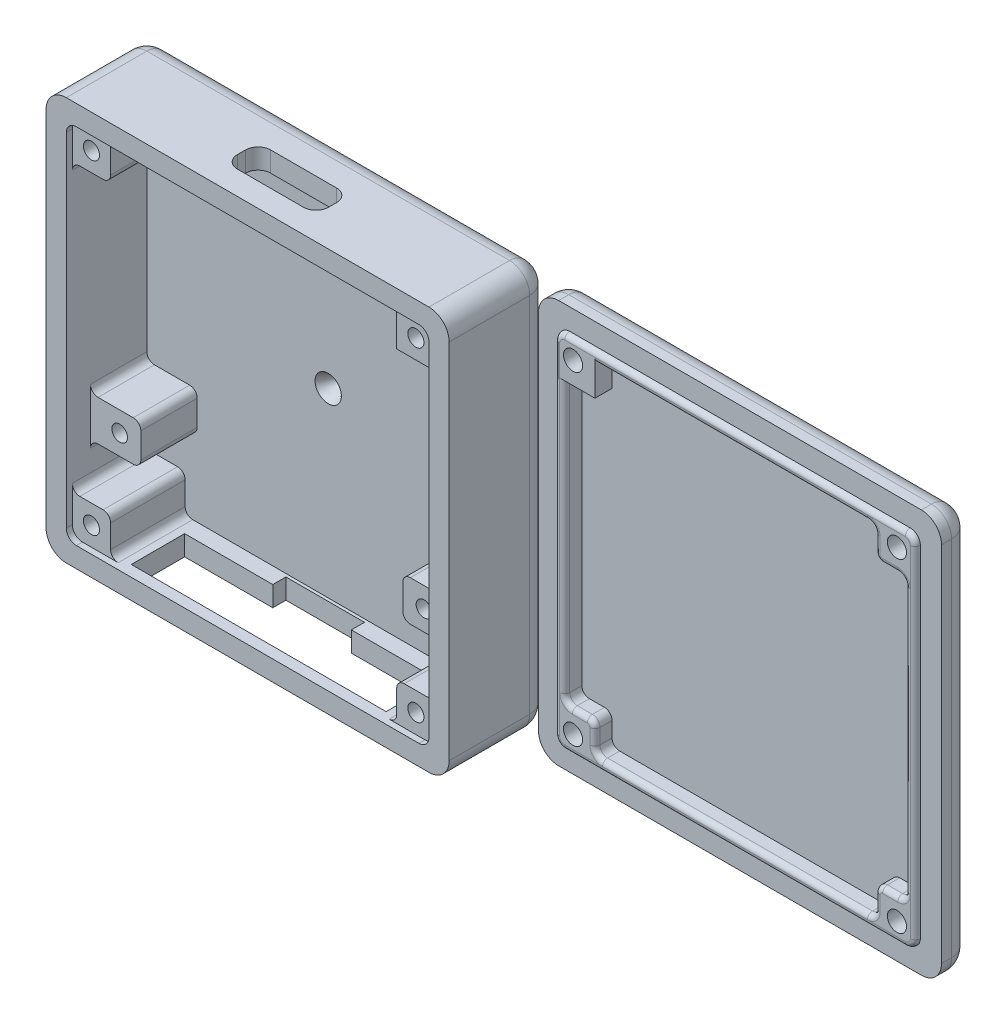
SolidWorks part; units mm, degrees
ref_plane "前视基准面" through (0, 0, 0) normal (0, 0, 1) x (1, 0, 0)
ref_plane "上视基准面" through (0, 0, 0) normal (0, 1, 0) x (1, 0, 0)
ref_plane "右视基准面" through (0, 0, 0) normal (1, 0, 0) x (0, 0, -1)
other "Configuration Table"
sketch "草图1" plane through (0, 0, 0) normal (0, 0, 1) x (1, 0, 0)
  line L6 (-20, 20) -> (20, 20)
  line L11 (-20, 20) -> (-20, -20)
  line L12 (-20, -20) -> (20, -20)
  line L13 (20, 20) -> (20, -20)
  line L14 (-20, 20) -> (20, -20) construction
  line L15 (-20, -20) -> (20, 20) construction
  point P0 (0, 0)
  dimension "D1" = 40
  dimension "D2" = 40
extrude "凸台-拉伸3" add sketch "草图1" along normal blind 10
fillet "圆角1" radius 2 8 edges at (20, -20, 5) (-20, -20, 5) (20, 20, 5) (-20, 20, 5) (0, 20, 0) (-20, 0, 0) (0, -20, 0) (20, 0, 0)
sketch "草图5" plane through (0, 0, 10) normal (0, 0, 1) x (1, 0, 0)
  line L1 (-17, 18) -> (17, 18)
  line L2 (-18, 17) -> (-18, -17)
  line L3 (-17, -18) -> (17, -18)
  line L4 (18, 17) -> (18, -17)
  line L5 (-18, 18) -> (18, -18) construction
  line L6 (-18, -18) -> (18, 18) construction
  arc A0 (-18, -17) -> (-17, -18) centre (-17, -17) ccw
  arc A1 (17, -18) -> (18, -17) centre (17, -17) ccw
  arc A2 (18, 17) -> (17, 18) centre (17, 17) ccw
  arc A3 (-17, 18) -> (-18, 17) centre (-17, 17) ccw
  point P0 (0, 0)
  dimension "D3" = 1
  dimension "D4" = 1
  dimension "D1" = 36
  dimension "D2" = 36
extrude "切除-拉伸2" cut sketch "草图5" against normal blind 8
sketch "草图6" plane through (0, 0, 0) normal (0, 0, -1) x (-1, 0, 0)
  line L0 (-18, -14.2) -> (-14.2, -14.2)
  line L1 (-18, -17) -> (-18, 17) construction
  line L2 (-14.2, -14.2) -> (-14.2, -18)
  line L3 (17, -18) -> (-17, -18) construction
  line L4 (14.2, 18) -> (14.2, 14.2)
  line L5 (-17, 18) -> (17, 18) construction
  line L6 (14.2, 14.2) -> (18, 14.2)
  line L7 (18, 17) -> (18, -17) construction
  line L8 (-18, -14.2) -> (-14.2, -18) construction
  line L9 (-14.2, -14.2) -> (-17.7071, -17.7071) construction
  line L10 (14.2, 18) -> (18, 14.2) construction
  line L11 (14.2, 14.2) -> (17.7071, 17.7071) construction
  line L12 (14.2, 18) -> (17, 18)
  line L13 (18, 17) -> (18, 14.2)
  line L14 (-18, -14.2) -> (-18, -17)
  line L15 (-17, -18) -> (-14.2, -18)
  line L16 (0, 18) -> (0, -18) construction
  line L17 (-17, 18) -> (17, 18) construction
  line L18 (18, 0) -> (-18, 0) construction
  line L19 (17, -18) -> (14.2, -18)
  line L20 (18, -14.2) -> (18, -17)
  line L21 (18, -14.2) -> (14.2, -14.2)
  line L22 (14.2, -14.2) -> (14.2, -18)
  line L23 (18, 17) -> (18, -17) construction
  line L24 (-18, -17) -> (-18, 17) construction
  line L25 (-14.2, 18) -> (-17, 18)
  line L26 (-18, 17) -> (-18, 14.2)
  line L27 (-14.2, 14.2) -> (-18, 14.2)
  line L28 (-14.2, 18) -> (-14.2, 14.2)
  arc A0 (-18, -17) -> (-17, -18) centre (-17, -17) ccw
  arc A1 (17, 18) -> (18, 17) centre (17, 17) cw
  circle A2 centre (-16.1, -16.1) radius 0.8
  circle A3 centre (16.1, -16.1) radius 0.8
  arc A4 (18, -17) -> (17, -18) centre (17, -17) cw
  circle A5 centre (16.1, 16.1) radius 0.8
  arc A6 (-17, 18) -> (-18, 17) centre (-17, 17) ccw
  circle A7 centre (-16.1, 16.1) radius 0.8
  point P25 (-18, -18)
  dimension "D5" = 1.6
  dimension "D6" = 1.6
  dimension "D7" = 1
  dimension "D8" = 1
  dimension "D9" = 1.6
  dimension "D1" = 3.8
  dimension "D2" = 3.8
  dimension "D3" = 3.8
  dimension "D4" = 3.8
extrude "凸台-拉伸4" add sketch "草图6" against normal blind 9.4
sketch "草图8" plane through (0, 0, 0) normal (0, 0, -1) x (-1, 0, 0)
  line L0 (-17, 18) -> (17, 18) construction
  line L1 (-14.2, 18) -> (14.2, 18) construction
  line L2 (0, 18) -> (0, -18) construction
  line L9 (-18, -6.588) -> (-13, -6.588)
  line L11 (-18, -14.2) -> (-18, 14.2) construction
  line L12 (-13, -6.588) -> (-13, -10.588)
  line L13 (-13, -10.588) -> (-18, -10.588)
  line L15 (-18, -6.588) -> (-18, -10.588)
  line L21 (13, -6.588) -> (13, -10.588)
  line L22 (13, -10.588) -> (18, -10.588)
  line L23 (18, -6.588) -> (18, -10.588)
  line L24 (18, -6.588) -> (13, -6.588)
  circle A1 centre (-15.1, -8.588) radius 0.775
  circle A4 centre (15.1, -8.588) radius 0.775
  dimension "D4" = 1.55
  dimension "D5" = 26.588
  dimension "D6" = 15.1
  dimension "D10" = 5
  dimension "D11" = 4
extrude "凸台-拉伸5" add sketch "草图8" against normal blind 7.6
fillet "圆角2" radius 0.75 17 edges at (14.2, -18, 5.7) (14.2, -14.2, 5.7) (18, -14.2, 5.7) (18, -10.588, 4.8) (13, -10.588, 4.8) (13, -6.588, 4.8) (18, -6.588, 4.8) (-14.2, 18, 5.7) (-18, 14.2, 5.7) (-14.2, 14.2, 5.7) (-14.2, -14.2, 5.7) (-18, -14.2, 5.7) (-14.2, -18, 5.7) (-18, -10.588, 4.8) (-13, -10.588, 4.8) (-13, -6.588, 4.8) (-18, -6.588, 4.8)
sketch "草图9" plane through (0, 20, 0) normal (0, 1, 0) x (1, 0, 0)
  line L0 (0, 0) -> (0, -10) construction
  line L1 (-4.6145, -4.35) -> (4.4355, -4.35)
  line L2 (-4.6145, -4.35) -> (-4.6145, -7.65)
  line L3 (-4.6145, -7.65) -> (4.4355, -7.65)
  line L4 (4.4355, -4.35) -> (4.4355, -7.65)
  line L5 (-4.6145, -4.35) -> (4.4355, -7.65) construction
  line L6 (-4.6145, -7.65) -> (4.4355, -4.35) construction
  line L7 (18, -10) -> (-18, -10) construction
  point P0 (-0.0895, -6)
  dimension "D1" = 9.05
  dimension "D2" = 3.3
  dimension "D3" = 6
extrude "切除-拉伸3" cut sketch "草图9" against normal up to next
sketch "草图18" plane through (0, 0, 0) normal (0, 0, -1) x (-1, 0, 0)
  circle A0 centre (0, 0) radius 0.5
  dimension "D1" = 1
extrude "切除-拉伸10" cut sketch "草图18" against normal up to next
chamfer "倒角1" distance 1.4 angle 30 1 edges at (0.5, 0, 2)
fillet "圆角3" radius 1.25 4 edges at (4.4355, 19, 7.65) (4.4355, 19, 4.35) (-4.6145, 19, 4.35) (-4.6145, 19, 7.65)
sketch "草图10" plane through (0, -20, 0) normal (0, -1, 0) x (1, 0, 0)
  line L0 (0, 0) -> (0, 10) construction
  line L1 (12.65, 3.6) -> (3.9, 3.6)
  line L2 (12.65, 3.6) -> (12.65, 8.9)
  line L4 (-12.65, 3.6) -> (-12.65, 8.9)
  line L5 (12.65, 3.6) -> (-12.65, 8.9) construction
  line L6 (12.65, 8.9) -> (-12.65, 3.6) construction
  line L7 (-18, 10) -> (18, 10) construction
  line L13 (-3.9, 3.6) -> (-3.9, 2.3)
  line L14 (-3.9, 2.3) -> (3.9, 2.3)
  line L15 (3.9, 2.3) -> (3.9, 3.6)
  line L16 (-3.9, 3.6) -> (-12.65, 3.6)
  line L17 (-12.65, 8.9) -> (-11.18, 8.9)
  line L18 (-10.78, 8.9) -> (10.78, 8.9)
  line L19 (10.78, 9.15) -> (10.78, 8.9) construction
  line L20 (-11.18, 8.9) -> (-11.18, 9.15) construction
  line L21 (-11.18, 9.15) -> (-10.78, 9.15) construction
  line L22 (-10.78, 9.15) -> (-10.78, 8.9) construction
  line L23 (11.18, 9.15) -> (10.78, 9.15) construction
  line L24 (11.18, 8.9) -> (11.18, 9.15) construction
  line L25 (11.18, 8.9) -> (12.65, 8.9)
  line L26 (10.78, 8.9) -> (11.18, 8.9)
  line L27 (-11.18, 8.9) -> (-10.78, 8.9)
  point P0 (0, 6.25)
  dimension "D1" = 6.25
  dimension "D2" = 25.3
  dimension "D3" = 5.3
  dimension "D6" = 7.8
  dimension "D7" = 1.3
  dimension "D8" = 0.25
extrude "切除-拉伸4" cut sketch "草图10" against normal up to next
sketch "草图24" plane through (0, 0, 0) normal (0, 0, -1) x (-1, 0, 0)
  line L0 (-18, 0) -> (-65.7458, 0) construction
  line L2 (0, 0) -> (-41.8729, 0) construction
  line L10 (-21.8729, 20) -> (-61.8729, 20)
  line L11 (-21.8729, 20) -> (-21.8729, -20)
  line L12 (-21.8729, -20) -> (-61.8729, -20)
  line L13 (-61.8729, 20) -> (-61.8729, -20)
  line L14 (-21.8729, 20) -> (-61.8729, -20) construction
  line L15 (-21.8729, -20) -> (-61.8729, 20) construction
  point P5 (-41.8729, 0)
  dimension "D3" = 40
  dimension "D4" = 40
extrude "凸台-拉伸6" add sketch "草图24" against normal blind 1.8 separate body
sketch "草图27" plane through (0, 0, 0) normal (0, 0, 1) x (1, 0, 0)
  line L0 (23.9229, 17.95) -> (59.8229, -17.95) construction
  line L9 (59.8229, 17.95) -> (23.9229, -17.95) construction
  line L10 (24.4729, 0) -> (59.2729, 0) construction
  line L11 (24.4729, 17.4) -> (59.2729, 17.4) construction
  line L12 (24.4729, 17.4) -> (24.4729, -17.4) construction
  line L13 (24.4729, -17.4) -> (59.2729, -17.4) construction
  line L14 (59.2729, 17.4) -> (59.2729, -17.4) construction
  line L15 (24.4729, 17.4) -> (59.2729, -17.4) construction
  line L16 (24.4729, -17.4) -> (59.2729, 17.4) construction
  line L18 (23.9229, -17.95) -> (23.9229, -14.2)
  line L19 (23.9229, -17.95) -> (27.6729, -17.95)
  line L20 (27.6729, -17.95) -> (27.6729, -14.2)
  line L21 (23.9229, -14.2) -> (27.6729, -14.2)
  line L22 (41.8729, 0) -> (41.8729, -17.4) construction
  line L23 (59.8229, -17.95) -> (56.0729, -17.95)
  line L24 (59.8229, -17.95) -> (59.8229, -14.2)
  line L25 (59.8229, -14.2) -> (56.0729, -14.2)
  line L26 (56.0729, -17.95) -> (56.0729, -14.2)
  line L32 (23.9229, 14.2) -> (27.6729, 14.2)
  line L33 (59.8229, 17.95) -> (56.0729, 17.95)
  line L34 (56.0729, 17.95) -> (56.0729, 14.2)
  line L35 (59.8229, 14.2) -> (56.0729, 14.2)
  line L36 (59.8229, 17.95) -> (59.8229, 14.2)
  line L41 (27.6729, 17.95) -> (27.6729, 14.2)
  line L42 (59.8229, 17.95) -> (56.1729, 17.95) construction
  line L43 (23.9229, 17.95) -> (27.6729, 17.95)
  line L44 (23.9229, 14.2) -> (23.9229, 17.95)
  circle A2 centre (25.7979, -16.075) radius 0.95
  circle A3 centre (57.9479, -16.075) radius 0.95
  circle A4 centre (57.9479, 16.075) radius 0.95
  circle A6 centre (25.7979, 16.075) radius 0.95
  point P8 (41.8729, 0)
  dimension "D3" = 34.8
  dimension "D4" = 34.8
extrude "凸台-拉伸7" add sketch "草图27" along normal blind 3
sketch "草图29" plane through (0, 0, 1.8) normal (0, 0, 1) x (1, 0, 0)
  line L0 (27.9729, -13.9) -> (55.7729, 13.9) construction
  line L5 (27.9729, 13.9) -> (55.7729, -13.9) construction
  line L11 (27.9729, 13.9) -> (55.7729, -13.9) construction
  line L12 (27.9729, -13.9) -> (55.7729, 13.9) construction
  line L15 (24.9729, 13.9) -> (27.9729, 13.9)
  line L16 (27.9729, 16.9) -> (27.9729, 13.9)
  line L19 (58.7729, 13.9) -> (55.7729, 13.9)
  line L20 (55.7729, 16.9) -> (55.7729, 13.9)
  line L23 (58.7729, -13.9) -> (55.7729, -13.9)
  line L24 (55.7729, -16.9) -> (55.7729, -13.9)
  line L27 (24.9729, -13.9) -> (27.9729, -13.9)
  line L28 (27.9729, -16.9) -> (27.9729, -13.9)
  line L29 (24.9729, 13.9) -> (24.9729, -13.9)
  line L30 (27.9729, -16.9) -> (55.7729, -16.9)
  line L31 (27.9729, 16.9) -> (55.7729, 16.9)
  line L32 (58.7729, 13.9) -> (58.7729, -13.9)
  line L34 (21.8729, 20) -> (61.8729, 20)
  line L35 (21.8729, 20) -> (21.8729, -20)
  line L36 (21.8729, -20) -> (61.8729, -20)
  line L37 (61.8729, 20) -> (61.8729, -20)
  line L38 (21.8729, 20) -> (61.8729, -20) construction
  line L39 (21.8729, -20) -> (61.8729, 20) construction
  point P0 (41.8729, 0)
  point P6 (41.8729, 0)
  point P10 (41.8729, 0)
extrude "凸台-拉伸8" add sketch "草图29" along normal blind 1.7
sketch "草图31" plane through (0, 0, 3.5) normal (0, 0, 1) x (1, 0, 0)
  line L14 (23.9729, 17.9) -> (23.9729, -17.9)
  line L15 (23.9729, -17.9) -> (59.7729, -17.9)
  line L16 (59.7729, -17.9) -> (59.7729, 17.9)
  line L17 (59.7729, 17.9) -> (23.9729, 17.9)
  line L22 (61.8729, -20) -> (61.8729, 20)
  line L23 (61.8729, 20) -> (21.8729, 20)
  line L24 (21.8729, 20) -> (21.8729, -20)
  line L25 (21.8729, -20) -> (61.8729, -20)
extrude "切除-拉伸18" cut sketch "草图31" against normal blind 0.5
fillet "圆角4" radius 2 8 edges at (41.8729, 20, 0) (21.8729, 0, 0) (41.8729, -20, 0) (61.8729, 0, 0) (21.8729, -20, 1.5) (61.8729, -20, 1.5) (21.8729, 20, 1.5) (61.8729, 20, 1.5)
fillet "圆角5" radius 0.75 9 edges at (27.9729, -16.9, 2.65) (27.9729, -13.9, 2.65) (24.9729, -13.9, 2.65) (55.7729, -16.9, 2.65) (55.7729, -13.9, 2.65) (58.7729, -13.9, 2.65) (58.7729, 13.9, 2.65) (55.7729, 13.9, 2.65) (55.7729, 16.9, 2.65)
fillet "圆角6" radius 1 4 edges at (23.9729, -17.9, 3.25) (59.7729, -17.9, 3.25) (59.7729, 17.9, 3.25) (23.9729, 17.9, 3.25)
fillet "圆角7" radius 0.5 27 edges at (24.2658, 17.6071, 3.5) (41.8729, 17.9, 3.5) (59.48, 17.6071, 3.5) (59.7729, 0, 3.5) (59.48, -17.6071, 3.5) (41.8729, -17.9, 3.5) (24.2658, -17.6071, 3.5) (23.9729, 0, 3.5) (28.1926, -16.6803, 3.5) (41.8729, -16.9, 3.5) (55.5532, -16.6803, 3.5) (55.7729, -15.4, 3.5) (55.9926, -14.1197, 3.5) (57.2729, -13.9, 3.5) (58.5532, -13.6803, 3.5) (58.7729, 0, 3.5) (58.5532, 13.6803, 3.5) (57.2729, 13.9, 3.5) (55.9926, 14.1197, 3.5) (55.7729, 15.4, 3.5) (55.5532, 16.6803, 3.5) (41.4979, 16.9, 3.5) (24.9729, 0.375, 3.5) (25.1926, -13.6803, 3.5) (26.4729, -13.9, 3.5) (27.7532, -14.1197, 3.5) (27.9729, -15.4, 3.5)
sketch "草图28" plane through (0, 0, 0) normal (0, 0, -1) x (-1, 0, 0)
  line L0 (-41.8729, 18) -> (-41.8729, -18) construction
  line L1 (-23.8729, 18) -> (-59.8729, 18) construction
  line L2 (-59.8729, -18) -> (-23.8729, -18) construction
  circle A1 centre (-25.7979, -16.075) radius 1.65
  circle A2 centre (-57.9479, -16.075) radius 1.65
  circle A5 centre (-57.9479, 16.075) radius 1.65
  circle A6 centre (-25.7979, 16.075) radius 1.65
  dimension "D2" = 3.3
  dimension "D3" = 3.3
  dimension "D4" = 3.3
extrude "切除-拉伸17" cut sketch "草图28" against normal blind 1.9
sketch "草图32" plane through (0, 0, 0) normal (0, 0, -1) x (-1, 0, 0)
  line L0 (-41.8729, -18) -> (-41.8729, 18) construction
  line L1 (-59.8729, -18) -> (-23.8729, -18) construction
  line L2 (-23.8729, 18) -> (-59.8729, 18) construction
  circle A0 centre (-57.9479, 16.075) radius 0.95
  circle A4 centre (-57.9479, -16.075) radius 0.95
  circle A5 centre (-25.7979, -16.075) radius 0.95
  circle A6 centre (-25.7979, 16.075) radius 0.95
  dimension "D1" = 1.9
  dimension "D3" = 1.9
  dimension "D4" = 1.9
extrude "切除-拉伸19" cut sketch "草图32" against normal up to next
